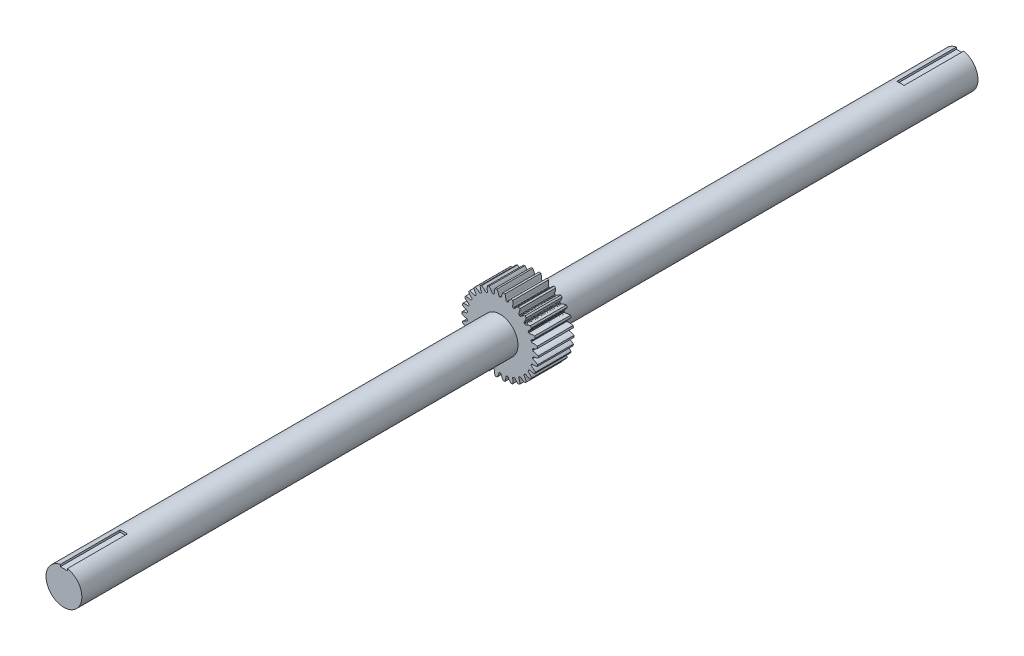
SolidWorks part; units mm, degrees
ref_plane "前视基准面" through (0, 0, 0) normal (0, 0, 1) x (1, 0, 0)
ref_plane "上视基准面" through (0, 0, 0) normal (0, 1, 0) x (1, 0, 0)
ref_plane "右视基准面" through (0, 0, 0) normal (1, 0, 0) x (0, 0, -1)
sketch "草图1" plane through (0, 0, 0) normal (0, 0, 1) x (1, 0, 0)
  circle A0 centre (0, 0) radius 32
extrude "凸台-拉伸1" add sketch "草图1" along normal blind 30
ref_axis "基准轴1" through (0, 0, 30) along (0, 0, -1)
sketch "草图2" plane through (0, 0, 0) normal (0, 0, 1) x (1, 0, 0)
  line L0 (0, 0) -> (0, 32) construction
  circle A0 centre (0, 0) radius 32 construction
  arc A1 (0.2911, 27.4985) -> (-0.2911, 27.4985) centre (0, 0) ccw
  arc A2 (6.7326, 36.3811) -> (-6.7326, 36.3811) centre (0, 0) ccw
  spline S0 degree 3 poles (0.2911, 27.4985) (1.0165, 27.626) (1.0206, 28.0943) (1.118, 28.5772) (1.1399, 28.6763) (1.1665, 28.7858) (1.1981, 28.9058) (1.2353, 29.0359) (1.2783, 29.1761) (1.3276, 29.326) (1.3837, 29.4856) (1.4469, 29.6547) (1.5176, 29.8328) (1.5962, 30.02) (1.6832, 30.2158) (1.7788, 30.4201) (1.8834, 30.6325) (1.9975, 30.8529) (2.1213, 31.0808) (2.2552, 31.3159) (2.3996, 31.5581) (2.5548, 31.8069) (2.7211, 32.0619) (2.8987, 32.323) (3.0881, 32.5896) (3.2895, 32.8614) (3.5032, 33.1381) (3.7295, 33.4192) (3.9685, 33.7044) (4.2207, 33.9933) (4.4861, 34.2854) (4.7651, 34.5803) (5.0578, 34.8776) (5.3645, 35.1769) (5.6854, 35.4777) (6.1378, 35.8852) (6.4907, 36.1841) (6.7326, 36.3811) knots 0 0 0 0 0.115324 0.123413 0.132512 0.142623 0.153745 0.165878 0.179022 0.193177 0.208343 0.22452 0.241708 0.259907 0.279117 0.299338 0.320571 0.342814 0.366068 0.390334 0.41561 0.441898 0.469196 0.497506 0.526827 0.557158 0.588501 0.620855 0.65422 0.688595 0.723982 0.76038 0.797789 0.836209 0.87564 0.916083 1 1 1 1
  spline S1 degree 3 poles (-0.2911, 27.4985) (-1.0165, 27.626) (-1.0206, 28.0943) (-1.118, 28.5772) (-1.1399, 28.6763) (-1.1665, 28.7858) (-1.1981, 28.9058) (-1.2353, 29.0359) (-1.2783, 29.1761) (-1.3276, 29.326) (-1.3837, 29.4856) (-1.4469, 29.6547) (-1.5176, 29.8328) (-1.5962, 30.02) (-1.6832, 30.2158) (-1.7788, 30.4201) (-1.8834, 30.6325) (-1.9975, 30.8529) (-2.1213, 31.0808) (-2.2552, 31.3159) (-2.3996, 31.5581) (-2.5548, 31.8069) (-2.7211, 32.0619) (-2.8987, 32.323) (-3.0881, 32.5896) (-3.2895, 32.8614) (-3.5032, 33.1381) (-3.7295, 33.4192) (-3.9685, 33.7044) (-4.2207, 33.9933) (-4.4861, 34.2854) (-4.7651, 34.5803) (-5.0578, 34.8776) (-5.3645, 35.1769) (-5.6854, 35.4777) (-6.1378, 35.8852) (-6.4907, 36.1841) (-6.7326, 36.3811) knots 0 0 0 0 0.115324 0.123413 0.132512 0.142623 0.153745 0.165878 0.179022 0.193177 0.208343 0.22452 0.241708 0.259907 0.279117 0.299338 0.320571 0.342814 0.366068 0.390334 0.41561 0.441898 0.469196 0.497506 0.526827 0.557158 0.588501 0.620855 0.65422 0.688595 0.723982 0.76038 0.797789 0.836209 0.87564 0.916083 1 1 1 1
extrude "切除-拉伸1" cut sketch "草图2" along normal through all
pattern_circular "阵列(圆周)1" count 30 every 12 about axis through (0, 0, 30) along (0, 0, -1) of "切除-拉伸1"
sketch "草图3" plane through (0, 0, 0) normal (0, 0, 1) x (1, 0, 0)
  circle A0 centre (0, 0) radius 30 construction
  dimension "Dn" = 60
sketch "草图4" plane through (0, 0, 30) normal (0, 0, 1) x (1, 0, 0)
  circle A0 centre (0, 0) radius 15
  dimension "D1" = 30
extrude "凸台-拉伸2" add sketch "草图4" along normal blind 365
sketch "草图5" plane through (0, 0, 0) normal (0, 0, -1) x (-1, 0, 0)
  circle A0 centre (0, 0) radius 15
  dimension "D1" = 30
extrude "凸台-拉伸3" add sketch "草图5" along normal blind 355
ref_plane "基准面1" through (0, 15, 0) normal (0, 1, 0) x (1, 0, 0)
sketch "草图6" plane through (0, 15, 0) normal (0, 1, 0) x (1, 0, 0)
  line L0 (15, 355) -> (-15, 355) construction
  line L1 (-3, 305) -> (3, 305)
  line L2 (-3, 305) -> (-3, 355)
  line L3 (-3, 355) -> (3, 355)
  line L4 (3, 305) -> (3, 355)
  line L5 (0, 355) -> (0, 305) construction
  line L6 (-3, 330) -> (3, 330) construction
  line L7 (-15, -395) -> (15, -395) construction
  line L8 (-3, -345) -> (3, -345)
  line L9 (-3, -345) -> (-3, -395)
  line L10 (-3, -395) -> (3, -395)
  line L11 (3, -345) -> (3, -395)
  line L12 (0, -395) -> (0, -345) construction
  line L13 (-3, -370) -> (3, -370) construction
  point P0 (0, 330)
  point P6 (0, -370)
  point P12 (0, 0)
  dimension "D1" = 6
  dimension "D2" = 50
  dimension "D3" = 6
  dimension "D4" = 50
extrude "切除-拉伸2" cut sketch "草图6" against normal blind 2
